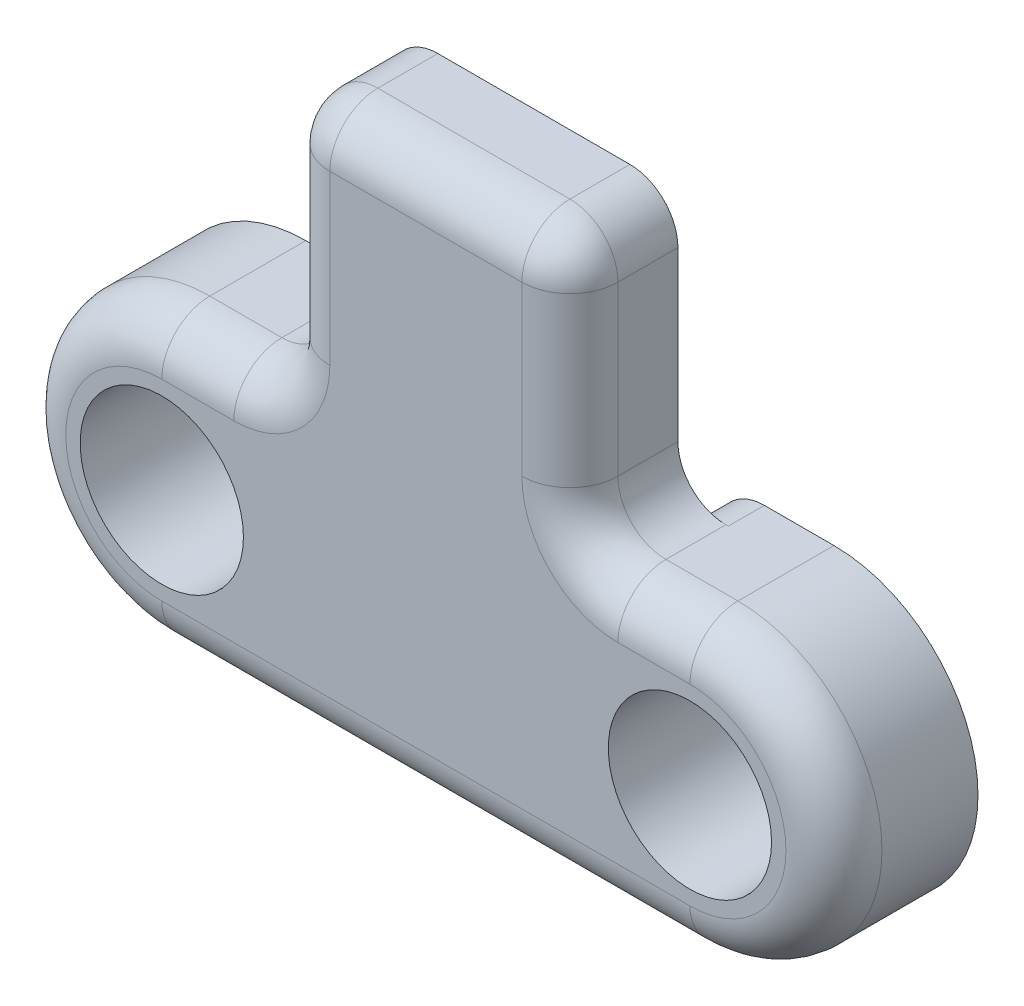
SolidWorks part; units mm, degrees
material "ABS"
ref_plane "Front Plane" through (0, 0, 0) normal (0, 0, 1) x (1, 0, 0)
ref_plane "Top Plane" through (0, 0, 0) normal (0, 1, 0) x (1, 0, 0)
ref_plane "Right Plane" through (0, 0, 0) normal (1, 0, 0) x (0, 0, -1)
sketch "Sketch1" plane through (0, 0, 0) normal (0, 0, 1) x (1, 0, 0)
  line L0 (-5.5, 0) -> (5.5, 0)
  line L1 (-5.5, 0) -> (5.5, 0) construction
  line L2 (-5.5, 3) -> (5.5, 3)
  line L3 (-5.5, -3) -> (5.5, -3)
  line L5 (-3, 3) -> (3, 3)
  line L6 (-3, 3) -> (-3, 8.5)
  line L7 (-3, 8.5) -> (3, 8.5)
  line L8 (3, 3) -> (3, 8.5)
  circle A0 centre (5.5, 0) radius 1.7
  circle A1 centre (-5.5, 0) radius 1.7
  arc A2 (-5.5, 3) -> (-5.5, -3) centre (-5.5, 0) ccw
  arc A3 (5.5, -3) -> (5.5, 3) centre (5.5, 0) ccw
  point P4 (0, 0)
  point P8 (0, 0)
  point P17 (0, 8.5)
  point P18 (0, 3)
  dimension "D1" = 3.4
  dimension "D3" = 3
  dimension "D2" = 11
  dimension "D4" = 5.5
  dimension "D5" = 6
extrude "Boss-Extrude1" add sketch "Sketch1" along normal blind 3 contours L3 A3 L2 A2 A1 A0 | L6 L5 L8 L7 region at (-4.25, 2.8197, 0)
sketch "Sketch2" plane through (0, 0, 0) normal (0, 1, 0) x (1, 0, 0)
  line L0 (-5.5, 0) -> (-3, 0) construction
  line L1 (-3.05, 0) -> (3.05, 0)
  line L2 (-3.05, 0) -> (-3.05, -0.75)
  line L3 (-3.05, -0.75) -> (3.05, -0.75)
  line L4 (3.05, 0) -> (3.05, -0.75)
  point P6 (0, -0.75)
  dimension "D1" = 6.1
  dimension "D2" = 0.75
extrude "Cut-Extrude1" cut sketch "Sketch2" against normal through all both and the other way through all
fillet "Fillet2" radius 1 4 edges at (3, 3, 1.875) (-3, 3, 1.875) (3, 8.5, 1.875) (-3, 8.5, 1.875)
fillet "Fillet1" radius 1 16 edges at (-8.5, 0, 3) (0, -3, 3) (8.5, 0, 3) (3.05, -3, 0.375) (-3.05, -3, 0.375) (-4.75, 3, 3) (4.75, 3, 3) (3.2929, 3.2929, 3) (3, 5.75, 3) (2.7071, 8.2071, 3) (0, 8.5, 3) (-2.7071, 8.2071, 3) (-3, 5.75, 3) (-3.2929, 3.2929, 3) (-3.05, 3.6878, 0.375) (3.05, 3.6878, 0.375)
